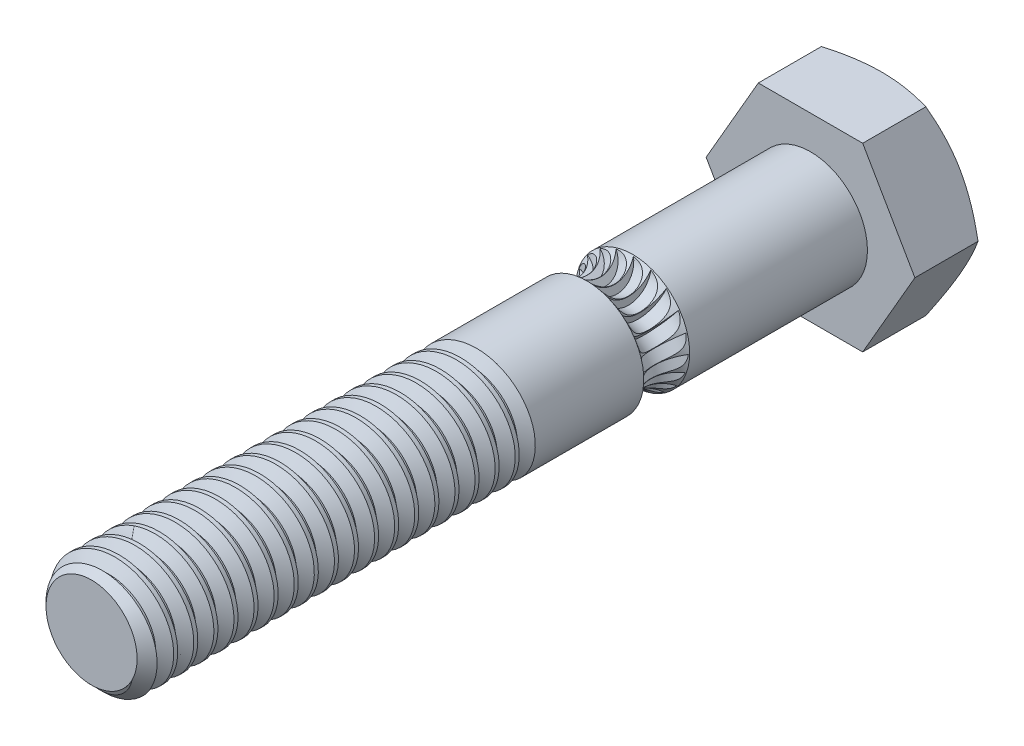
SolidWorks part; units mm, degrees
ref_plane "Front Plane" through (0, 0, 0) normal (0, 0, 1) x (1, 0, 0)
ref_plane "Top Plane" through (0, 0, 0) normal (0, 1, 0) x (1, 0, 0)
ref_plane "Right Plane" through (0, 0, 0) normal (1, 0, 0) x (0, 0, -1)
sketch "Sketch1" plane through (0, 0, 0) normal (0, 0, 1) x (1, 0, 0)
  circle A0 centre (0, 0) radius 4
  dimension "D1" = 8
extrude "Bolt Body" add sketch "Sketch1" along normal blind 50.5
ref_axis "Axis1" through (0, 0, -10.3812) along (0, 0, 1)
sketch "Sketch9" plane through (0, 0, 0) normal (1, 0, 0) x (0, 0, -1)
  line L0 (0, -4) -> (0, 4) construction
  line L1 (10.3812, 0) -> (-69.3803, 0) construction
  circle A0 centre (-14.1, 5.1594) radius 1.9844
  dimension "D1" = 3.9688
  dimension "D2" = 14.1
  dimension "D3" = 5.1594
revolve "Cut-Revolve1" cut sketch "Sketch9" angle 360 about axis through (0, 0, -10.3812) along (0, 0, 1)
sketch "Sketch3" plane through (0, 0, 0) normal (0, 0, 1) x (1, 0, 0)
  line L1 (7.3323, 0) -> (3.6662, 6.35)
  line L2 (3.6662, 6.35) -> (-3.6662, 6.35)
  line L3 (-3.6662, 6.35) -> (-7.3323, 0)
  line L4 (-7.3323, 0) -> (-3.6662, -6.35)
  line L5 (-3.6662, -6.35) -> (3.6662, -6.35)
  line L6 (3.6662, -6.35) -> (7.3323, 0)
  circle A1 centre (0, 0) radius 6.35 construction
  dimension "D2" = 12.7
extrude "Bolt Head" add sketch "Sketch3" against normal blind 5
sketch "Sketch5" plane through (0, 0, 0) normal (0, 1, 0) x (1, 0, 0)
  line L1 (0, 10.3812) -> (0, -69.3803) construction
  line L2 (-3.6662, 0) -> (-7.3323, 0) construction
  circle A0 centre (-3.95, -14.1) radius 1.5875
  dimension "D1" = 14.1
  dimension "D3" = 3.175
  dimension "D2" = 3.95
extrude "Cut-Extrude2" cut sketch "Sketch5" along normal through all from offset 1.31
pattern_circular "CirPattern1" count 20 every 18 about axis through (0, 0, 0) along (0, 0, 1) of "Cut-Extrude2"
chamfer "Chamfer1" distance 0.8 angle 45 1 edges at (4, 0, 50.5)
sketch "Sketch6" plane through (0, 0, -5) normal (0, 0, -1) x (-1, 0, 0)
  circle A0 centre (0, 0) radius 6.35
extrude "Cut-Extrude3" cut sketch "Sketch6" against normal blind 10 draft 60 flip side to cut
sketch "Sketch7" plane through (0, 0, 0) normal (1, 0, 0) x (0, 0, -1)
  line L0 (-50.5, 4) -> (-50.9619, 3.2)
  line L1 (-50.9619, 3.2) -> (-51.167, 3.2)
  line L2 (-51.167, 3.2) -> (-51.6289, 4)
  line L3 (-51.6289, 4) -> (-50.5, 4)
  line L4 (-50.5, 3.2) -> (-50.5, -3.2) construction
  line L5 (-15.7105, 4) -> (-49.7, 4) construction
  dimension "D1" = 60
  dimension "D2" = 60
  dimension "D3" = 0.8
  dimension "D4" = 1.1289
sketch "Sketch8" plane through (0, 0, 50.5) normal (0, 0, 1) x (1, 0, 0)
  circle A0 centre (0, 0) radius 4
curve "Helix/Spiral1" pitch 1.4111 height 28.2222 turns 20
sweep "Cut-Sweep1" cut profiles "Sketch7" path "Helix/Spiral1"
